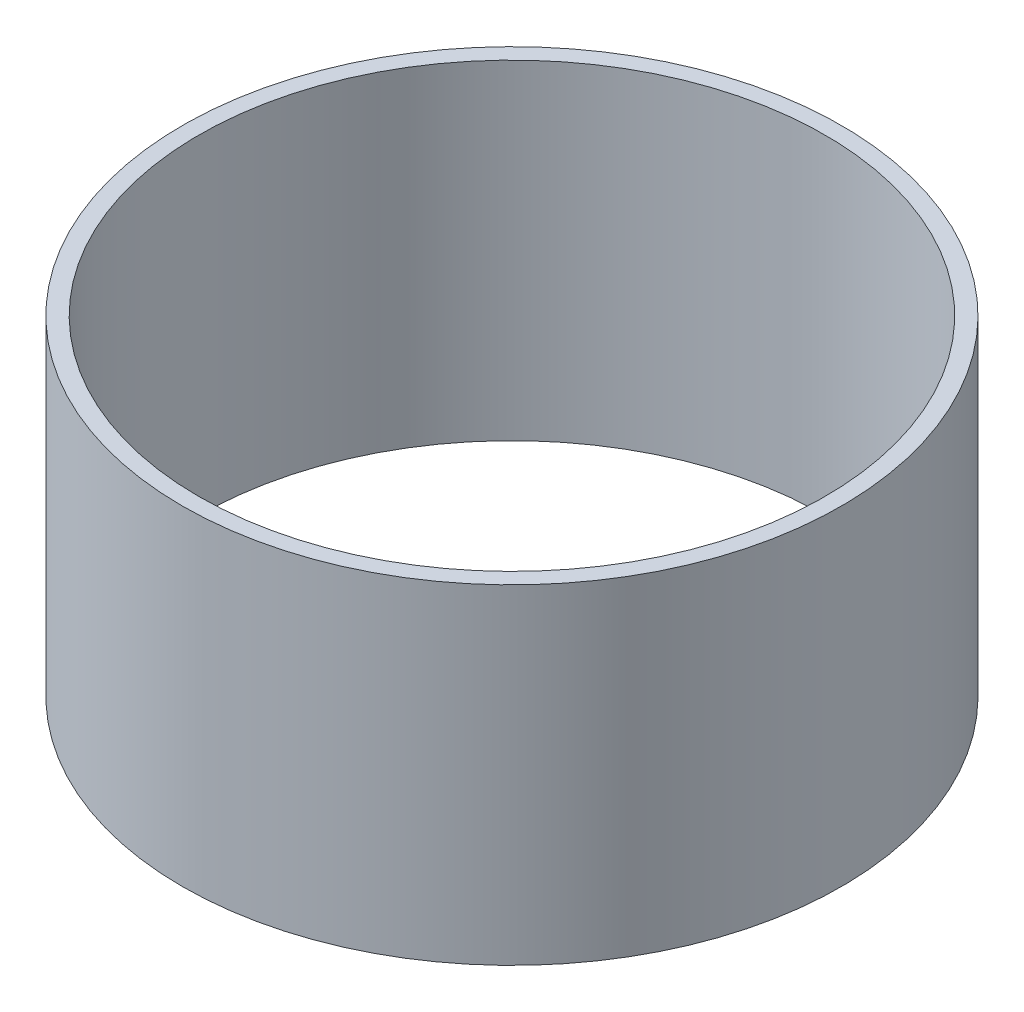
SolidWorks part; units mm, degrees
ref_plane "Front Plane" through (0, 0, 0) normal (0, 0, 1) x (1, 0, 0)
ref_plane "Top Plane" through (0, 0, 0) normal (0, 1, 0) x (1, 0, 0)
ref_plane "Right Plane" through (0, 0, 0) normal (1, 0, 0) x (0, 0, -1)
sketch "Sketch1" plane through (0, 0, 0) normal (0, 1, 0) x (1, 0, 0)
  circle A0 centre (0, 0) radius 100
  circle A1 centre (0, 0) radius 95
  dimension "D1" = 200
  dimension "D2" = 5
extrude "Boss-Extrude1" add sketch "Sketch1" along normal blind 100
